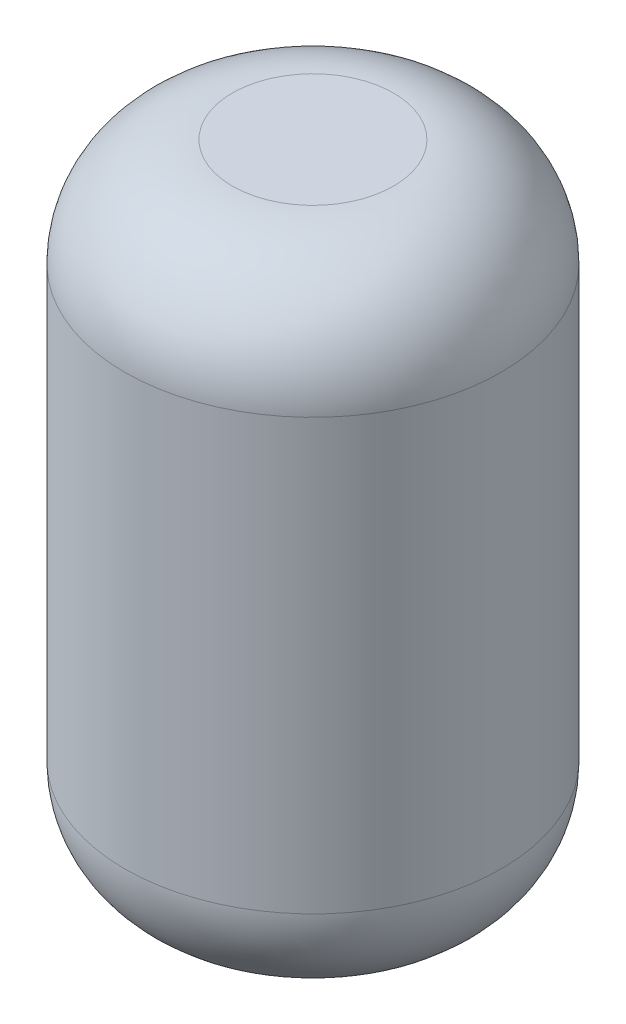
SolidWorks part; units mm, degrees
ref_plane "Front Plane" through (0, 0, 0) normal (0, 0, 1) x (1, 0, 0)
ref_plane "Top Plane" through (0, 0, 0) normal (0, 1, 0) x (1, 0, 0)
ref_plane "Right Plane" through (0, 0, 0) normal (1, 0, 0) x (0, 0, -1)
sketch "Sketch1" plane through (0, 0, 0) normal (0, 1, 0) x (1, 0, 0)
  circle A0 centre (0, 0) radius 2.1
  dimension "D1" = 4.2
extrude "Boss-Extrude1" add sketch "Sketch1" along normal blind 7.2
fillet "Fillet1" radius 1.2 2 edges at (0, 0, 2.1) (0, 7.2, 2.1)
